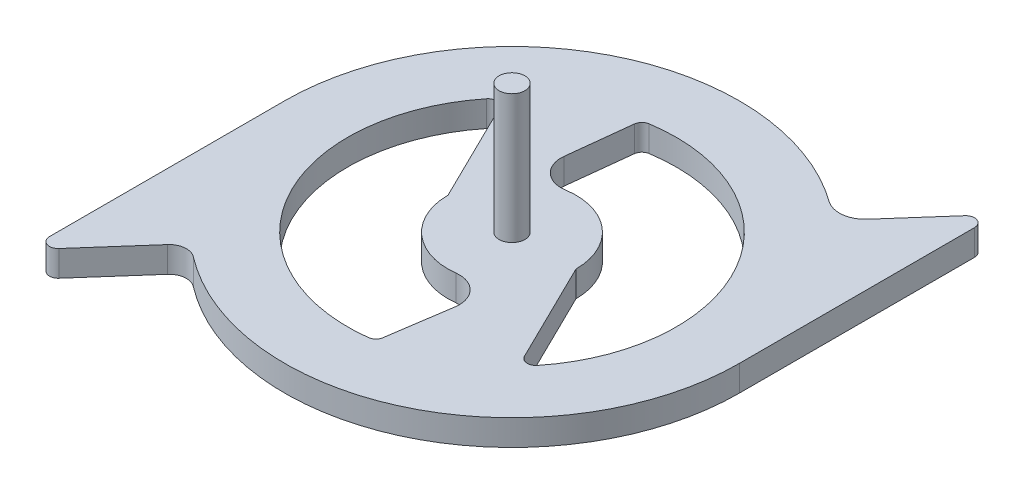
SolidWorks part; units mm, degrees
material "6061-T6 (SS)"
ref_plane "Plano frontal" through (0, 0, 0) normal (0, 0, 1) x (1, 0, 0)
ref_plane "Plano superior" through (0, 0, 0) normal (0, 1, 0) x (1, 0, 0)
ref_plane "Plano direito" through (0, 0, 0) normal (1, 0, 0) x (0, 0, -1)
sketch "Esboço1" plane through (0, 0, 0) normal (0, 1, 0) x (1, 0, 0)
  line L0 (-429.6893, 0) -> (21054.7778, 0) construction
  line L1 (0, -429.6893) -> (0, 21054.7778) construction
  line L2 (-26.4575, 0) -> (-26.4575, -30)
  line L3 (-26.4575, -30) -> (-17.5, -19.8431)
  line L4 (26.4575, 0) -> (26.4575, 30)
  line L5 (26.4575, 30) -> (17.5, 19.8431)
  line L6 (5.0097, -5.5052) -> (3.0302, -18.875)
  arc A0 (13.8948, -13.1295) -> (-3.6948, 18.7562) centre (0, 0) ccw
  arc A1 (17.5, 19.8431) -> (-26.4575, 0) centre (0, 0) ccw
  arc A2 (7.4434, 0) -> (-5.201, 5.3248) centre (0, 0) ccw
  arc A3 (-13.8948, 13.1295) -> (3.0302, -18.875) centre (0, 0) ccw
  arc A4 (-7.4434, 0) -> (5.0097, -5.5052) centre (0, 0) ccw
  arc A5 (-17.5, -19.8431) -> (26.4575, 0) centre (0, 0) ccw
  spline S0 degree 1 poles (-3.6948, 18.7562) (-5.201, 5.3248) knots 0 0 1 1
  spline S1 degree 1 poles (-13.8948, 13.1295) (-7.4434, 0) knots 0 0 1 1
  spline S2 degree 1 poles (7.4434, 0) (13.8948, -13.1295) knots 0 0 1 1
  dimension "D1" = 80
  dimension "D2" = 30
  dimension "D3" = 30
extrude "Ressalto-extrusão1" add sketch "Esboço1" along normal blind 3
fillet "Filete2" radius 1 1 edges at (26.4575, 1.5, -30)
fillet "Filete3" radius 1 1 edges at (-26.4575, 1.5, 30)
fillet "Filete4" radius 3 1 edges at (-5.201, 1.5, -5.3248)
fillet "Filete5" radius 1 1 edges at (-3.6948, 1.5, -18.7562)
fillet "Filete6" radius 2 1 edges at (-17.5, 1.5, 19.8431)
fillet "Filete8" radius 3 1 edges at (5.0097, 1.5, 5.5052)
fillet "Filete9" radius 1 1 edges at (3.0302, 1.5, 18.875)
fillet "Filete10" radius 1 1 edges at (13.8948, 1.5, 13.1295)
fillet "Filete11" radius 1 1 edges at (-13.8948, 1.5, -13.1295)
fillet "Filete12" radius 3 1 edges at (17.5, 1.5, -19.8431)
sketch "Esboço2" plane through (0, 3, 0) normal (0, 1, 0) x (1, 0, 0)
  circle A0 centre (0, 0) radius 1.5
extrude "Ressalto-extrusão2" add sketch "Esboço2" along normal blind 15
